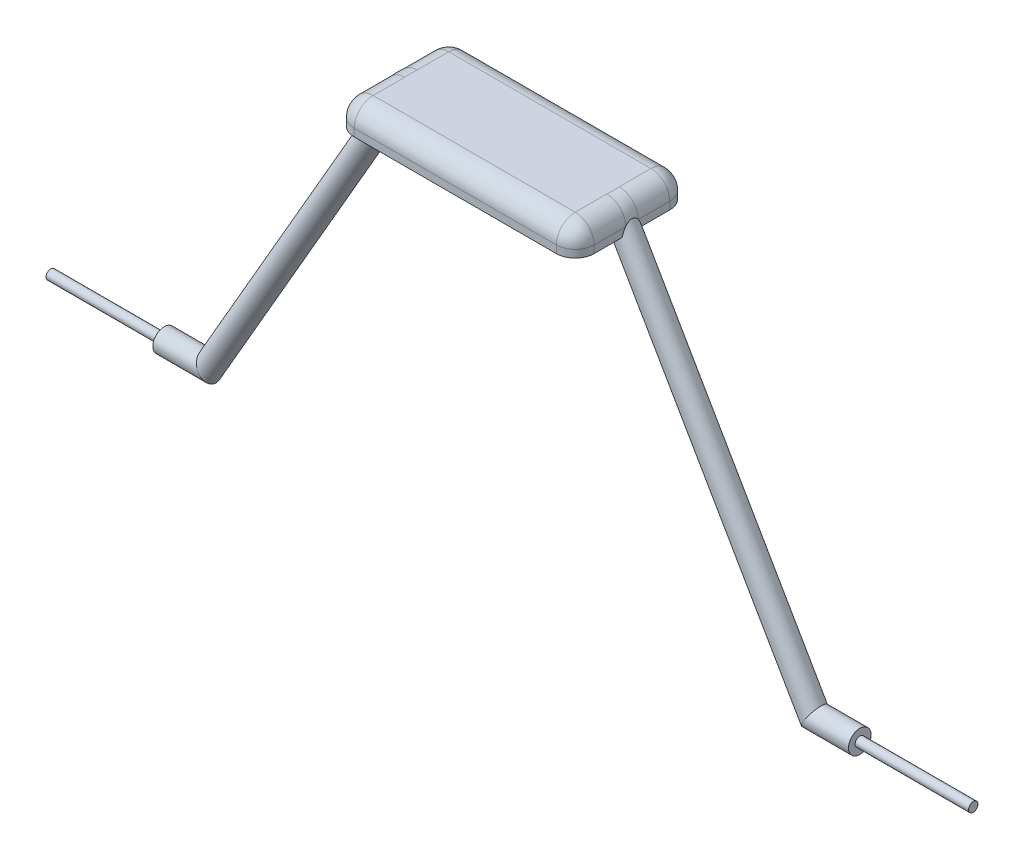
SolidWorks part; units mm, degrees
ref_plane "Front Plane" through (0, 0, 0) normal (0, 0, 1) x (1, 0, 0)
ref_plane "Top Plane" through (0, 0, 0) normal (0, 1, 0) x (1, 0, 0)
ref_plane "Right Plane" through (0, 0, 0) normal (1, 0, 0) x (0, 0, -1)
sketch "Sketch8" plane through (0, 0, 0) normal (0, 0, 1) x (1, 0, 0)
  line L0 (-30, 0) -> (30, 0)
  line L1 (-30, 0) -> (-80, -86.6025)
  line L2 (30, 0) -> (80, -86.6025)
  line L3 (-80, -86.6025) -> (-92, -86.6025)
  line L4 (80, -86.6025) -> (92, -86.6025)
  line L5 (-30, 0) -> (-30, -44.8993) construction
  line L6 (30, 0) -> (30, -49.8134) construction
  point P2 (0, 0)
  dimension "D1" = 60
  dimension "D2" = 100
  dimension "D3" = 30
  dimension "D4" = 30
  dimension "D5" = 100
  dimension "D6" = 12
  dimension "D7" = 12
ref_plane "Plane2" through (-92, 0, 0) normal (1, 0, 0) x (0, 0, -1)
sketch "Sketch12" plane through (-92, 0, 0) normal (1, 0, 0) x (0, 0, -1)
  line L0 (0, 0) -> (0, -86.6025) construction
  circle A0 centre (0, -86.6025) radius 3
  dimension "D1" = 6
sweep "Sweep4" add profiles "Sketch12" path "Sketch8"
sketch "Sketch13" plane through (-92, 0, 0) normal (-1, 0, 0) x (0, 0, 1)
  circle A0 centre (0, -86.6025) radius 1.25
  dimension "D1" = 2.5
extrude "Boss-Extrude4" add sketch "Sketch13" along normal blind 30
sketch "Sketch14" plane through (92, 0, 0) normal (1, 0, 0) x (0, 0, -1)
  circle A0 centre (0, -86.6025) radius 1.25
  dimension "D1" = 2.5
extrude "Boss-Extrude5" add sketch "Sketch14" along normal blind 30
sketch "Sketch15" plane through (0, 0, 0) normal (0, 1, 0) x (1, 0, 0)
  line L1 (-31.7321, 15) -> (31.7321, 15)
  line L2 (-31.7321, 15) -> (-31.7321, -15)
  line L3 (-31.7321, -15) -> (31.7321, -15)
  line L4 (31.7321, 15) -> (31.7321, -15)
  line L5 (-31.7321, 15) -> (31.7321, -15) construction
  line L6 (-31.7321, -15) -> (31.7321, 15) construction
  ellipse E0 centre (30, 0) end of major axis (30, 3) minor radius 1.7321 construction
  point P0 (0, 0)
  point P12 (31.7321, 0)
  dimension "D1" = 30
extrude "Boss-Extrude6" add sketch "Sketch15" along normal blind 7
fillet "Fillet6" radius 5 1 edges at (31.7321, 7, 0)
fillet "Fillet7" radius 5 1 edges at (-31.7321, 7, 0)
fillet "Fillet8" radius 5 5 edges at (31.7321, 1, 15) (30.2676, 5.5355, 15) (0, 7, 15) (-31.7321, 1, 15) (-30.2676, 5.5355, 15)
fillet "Fillet9" radius 5 5 edges at (0, 7, -15) (31.7321, 1, -15) (30.2676, 5.5355, -15) (-31.7321, 1, -15) (-30.2676, 5.5355, -15)
